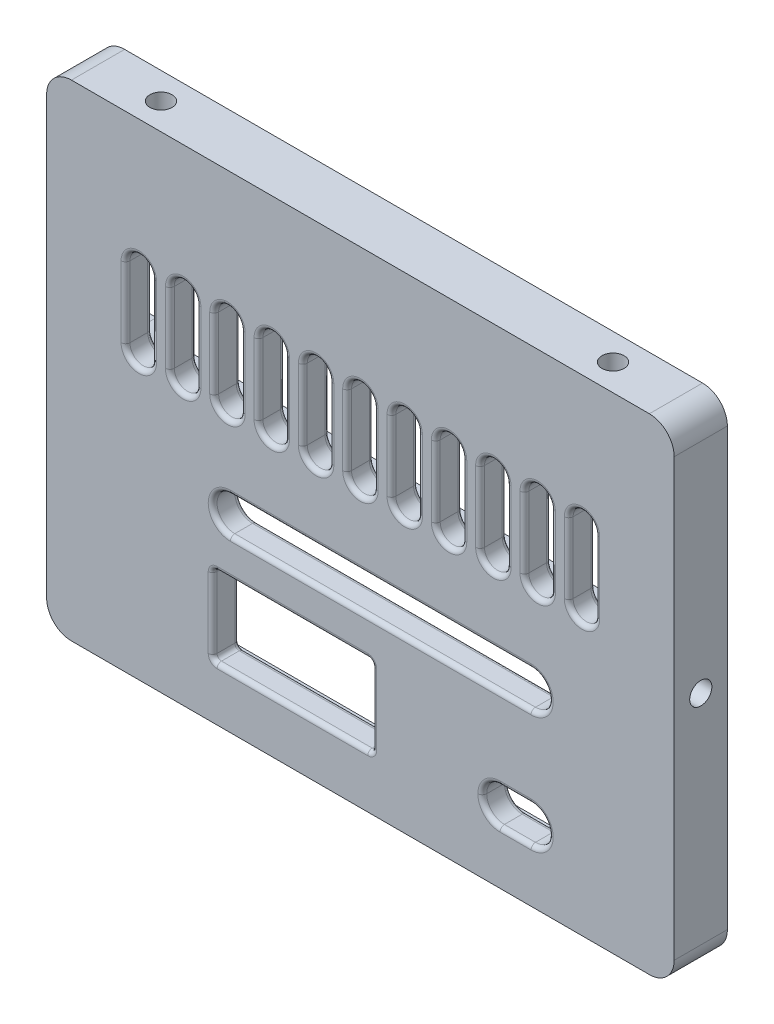
SolidWorks part; units mm, degrees
note: The reader was unsure of these and kept them because the rebuilt part matched: shared geometry of "Эскиз7<2>", "Эскиз9<2>".
ref_plane "Спереди" through (0, 0, 0) normal (0, 0, 1) x (1, 0, 0)
ref_plane "Сверху" through (0, 0, 0) normal (0, 1, 0) x (1, 0, 0)
ref_plane "Справа" through (0, 0, 0) normal (1, 0, 0) x (0, 0, -1)
sketch "Эскиз1" plane through (0, 0, 0) normal (0, 0, 1) x (1, 0, 0)
  line L0 (-32.6, 27.4) -> (32.6, 27.4)
  line L1 (35.4, -24.6) -> (35.4, 24.6)
  line L2 (-32.6, -27.4) -> (32.6, -27.4)
  line L3 (-35.4, 24.6) -> (-35.4, -24.6)
  arc A0 (-32.6, 27.4) -> (-35.4, 24.6) centre (-32.6, 24.6) ccw
  arc A1 (35.4, 24.6) -> (32.6, 27.4) centre (32.6, 24.6) ccw
  arc A2 (32.6, -27.4) -> (35.4, -24.6) centre (32.6, -24.6) ccw
  arc A3 (-35.4, -24.6) -> (-32.6, -27.4) centre (-32.6, -24.6) ccw
  point P11 (0, 27.4)
  point P14 (35.4, 0)
  point P17 (0, -27.4)
  point P20 (-35.4, 0)
  dimension "D3" = 2.8
  dimension "D1" = 70.8
  dimension "D2" = 54.8
extrude "Бобышка-Вытянуть1" add sketch "Эскиз1" along normal blind 3
sketch "Эскиз6" plane through (0, 0, 0) normal (0, 0, -1) x (-1, 0, 0)
  line L0 (-32.6, 27.4) -> (32.6, 27.4)
  line L1 (-35.4, 24.6) -> (-35.4, -24.6)
  line L2 (-32.6, -27.4) -> (32.6, -27.4)
  line L3 (35.4, -24.6) -> (35.4, 24.6)
  line L4 (-32.4, 24.4) -> (-28.5, 24.4)
  line L5 (32.4, -24.4) -> (32.4, -3)
  line L6 (-32.4, -24.4) -> (-28.5, -24.4)
  line L7 (-32.4, 24.4) -> (-32.4, 3)
  line L8 (0, 1.5) -> (0, -1.5) construction
  line L10 (-26.4, -1.5) -> (26.4, -1.5)
  line L11 (0, 32.9332) -> (0, -35.2988) construction
  line L12 (25.5, 21.9) -> (-25.5, 21.9) construction
  line L13 (25.5, -21.9) -> (-25.5, -21.9) construction
  line L14 (-22.5, 24.4) -> (22.5, 24.4)
  line L15 (-22.5, 16.4) -> (-28.5, 16.4)
  line L16 (-22.5, 16.4) -> (-22.5, 27.4)
  line L17 (-22.5, 27.4) -> (-28.5, 27.4)
  line L18 (-28.5, 16.4) -> (-28.5, 27.4)
  line L19 (-22.5, 16.4) -> (-28.5, 27.4) construction
  line L20 (-22.5, 27.4) -> (-28.5, 16.4) construction
  line L21 (22.5, 16.4) -> (28.5, 16.4)
  line L22 (22.5, 16.4) -> (22.5, 27.4)
  line L23 (22.5, 27.4) -> (28.5, 27.4)
  line L24 (28.5, 16.4) -> (28.5, 27.4)
  line L25 (22.5, 16.4) -> (28.5, 27.4) construction
  line L26 (22.5, 27.4) -> (28.5, 16.4) construction
  line L27 (22.5, -27.4) -> (28.5, -27.4)
  line L28 (22.5, -27.4) -> (22.5, -16.4)
  line L29 (22.5, -16.4) -> (28.5, -16.4)
  line L30 (28.5, -27.4) -> (28.5, -16.4)
  line L31 (22.5, -27.4) -> (28.5, -16.4) construction
  line L32 (22.5, -16.4) -> (28.5, -27.4) construction
  line L33 (-28.5, -27.4) -> (-22.5, -27.4)
  line L34 (-28.5, -27.4) -> (-28.5, -16.4)
  line L35 (-28.5, -16.4) -> (-22.5, -16.4)
  line L36 (-22.5, -27.4) -> (-22.5, -16.4)
  line L37 (-28.5, -27.4) -> (-22.5, -16.4) construction
  line L38 (-28.5, -16.4) -> (-22.5, -27.4) construction
  line L39 (-32.4, 24.4) -> (32.4, 24.4) construction
  line L40 (28.5, 24.4) -> (32.4, 24.4)
  line L41 (-32.4, -3) -> (-32.4, -24.4)
  line L42 (-32.4, 24.4) -> (-32.4, -24.4) construction
  line L43 (32.4, 3) -> (32.4, 24.4)
  line L44 (32.4, -24.4) -> (32.4, 24.4) construction
  line L45 (28.5, -24.4) -> (32.4, -24.4)
  line L46 (-32.4, -24.4) -> (32.4, -24.4) construction
  line L47 (-22.5, -24.4) -> (22.5, -24.4)
  line L48 (-2.6445, 0) -> (5.4228, 0) construction
  line L49 (-26.4, 1.5) -> (26.4, 1.5)
  line L50 (26.4, -3) -> (35.4, -3)
  line L51 (26.4, -3) -> (26.4, 3)
  line L52 (26.4, 3) -> (35.4, 3)
  line L53 (35.4, -3) -> (35.4, 3)
  line L54 (26.4, -3) -> (35.4, 3) construction
  line L55 (26.4, 3) -> (35.4, -3) construction
  line L56 (-26.4, -3) -> (-35.4, -3)
  line L57 (-26.4, -3) -> (-26.4, 3)
  line L58 (-26.4, 3) -> (-35.4, 3)
  line L59 (-35.4, -3) -> (-35.4, 3)
  line L60 (-26.4, -3) -> (-35.4, 3) construction
  line L61 (-26.4, 3) -> (-35.4, -3) construction
  arc A0 (-32.6, 27.4) -> (-35.4, 24.6) centre (-32.6, 24.6) ccw
  arc A1 (-35.4, -24.6) -> (-32.6, -27.4) centre (-32.6, -24.6) ccw
  arc A2 (32.6, -27.4) -> (35.4, -24.6) centre (32.6, -24.6) ccw
  arc A3 (35.4, 24.6) -> (32.6, 27.4) centre (32.6, 24.6) ccw
  arc A4 (32.4, 24.4) -> (32.4, 24.4) centre (32.4, 24.4) ccw
  arc A5 (32.4, -24.4) -> (32.4, -24.4) centre (32.4, -24.4) ccw
  arc A6 (-32.4, -24.4) -> (-32.4, -24.4) centre (-32.4, -24.4) ccw
  arc A7 (-32.4, 24.4) -> (-32.4, 24.4) centre (-32.4, 24.4) ccw
  point P38 (0, 0)
  point P48 (0, 21.9)
  point P51 (0, -21.9)
  point P75 (30.9, 0)
  point P81 (-30.9, 0)
  dimension "D3" = 6
  dimension "D4" = 11
  dimension "D5" = 51
  dimension "D6" = 6
  dimension "D7" = 9
  dimension "D2" = 3
extrude "Бобышка-Вытянуть3" add sketch "Эскиз6" along normal blind 3
fillet "Скругление7" radius 3 12 edges at (28.5, -16.4, -1.5) (22.5, -16.4, -1.5) (-22.5, -16.4, -1.5) (-28.5, -16.4, -1.5) (-28.5, 16.4, -1.5) (-22.5, 16.4, -1.5) (28.5, 16.4, -1.5) (22.5, 16.4, -1.5) (-26.4, 3, -1.5) (-26.4, -3, -1.5) (26.4, 3, -1.5) (26.4, -3, -1.5)
fillet "Скругление8" radius 3 16 edges at (-28.5, -21.9, -3) (-27.6213, -17.2787, -3) (-22.5, -21.9, -3) (22.5, -21.9, -3) (23.3787, -17.2787, -3) (28.5, -21.9, -3) (28.5, 21.9, -3) (22.5, 21.9, -3) (23.3787, 17.2787, -3) (-22.5, 21.9, -3) (-28.5, 21.9, -3) (-27.6213, 17.2787, -3) (-23.3787, -17.2787, -3) (27.6213, -17.2787, -3) (27.6213, 17.2787, -3) (-23.3787, 17.2787, -3)
fillet "Скругление9" radius 3 16 edges at (28.5, -21.9, 0) (22.5, -21.9, 0) (23.3787, -17.2787, 0) (-22.5, -21.9, 0) (-28.5, -21.9, 0) (-27.6213, -17.2787, 0) (-28.5, 21.9, 0) (-27.6213, 17.2787, 0) (-22.5, 21.9, 0) (22.5, 21.9, 0) (23.3787, 17.2787, 0) (28.5, 21.9, 0) (27.6213, -17.2787, 0) (-23.3787, -17.2787, 0) (-23.3787, 17.2787, 0) (27.6213, 17.2787, 0)
sketch "Эскиз7" plane through (0, -27.4, 0) normal (0, -1, 0) x (1, 0, 0)
  line L0 (0, 26.5617) -> (0, -19.5255) construction
  line L1 (25.5, 0) -> (-25.5, 0) construction
  circle A0 centre (-25.5, 0) radius 1.25
  circle A1 centre (25.5, 0) radius 1.25
  point P6 (0, 0)
  dimension "D2" = 2.5
  dimension "D1" = 51
extrude "Вырез-Вытянуть6" cut sketch "Эскиз7" against normal blind 9
extrude "Вырез-Вытянуть7" cut sketch "Эскиз7<2>" along normal blind 9 from offset 54.8 offset against normal yes
sketch "Эскиз7<2>" plane through (0, -27.4, 0) normal (0, -1, 0) x (1, 0, 0) same geometry as "Эскиз7"
sketch "Эскиз9" plane through (35.4, 0, 0) normal (1, 0, 0) x (0, 0, -1)
  circle A0 centre (0, 0) radius 1.25
  dimension "D1" = 2.5
extrude "Вырез-Вытянуть9" cut sketch "Эскиз9" against normal blind 7
extrude "Вырез-Вытянуть10" cut sketch "Эскиз9<2>" along normal blind 7 from offset 70.8 offset against normal yes
sketch "Эскиз9<2>" plane through (35.4, 0, 0) normal (1, 0, 0) x (0, 0, -1) same geometry as "Эскиз9"
sketch "Эскиз10" plane through (0, 0, 3) normal (0, 0, 1) x (1, 0, 0)
  line L0 (-47.1202, 8.54) -> (60.2518, 8.54) construction
  line L1 (-32.6, -27.4) -> (32.6, -27.4) construction
  line L2 (0, 11.8501) -> (0, -8.9997) construction
  line L3 (0, 12.54) -> (0, 4.54) construction
  line L4 (1.5, 12.54) -> (1.5, 4.54)
  line L5 (-1.5, 12.54) -> (-1.5, 4.54)
  line L6 (5, 12.54) -> (5, 4.54) construction
  line L7 (6.5, 12.54) -> (6.5, 4.54)
  line L8 (3.5, 12.54) -> (3.5, 4.54)
  line L9 (10, 12.54) -> (10, 4.54) construction
  line L10 (11.5, 12.54) -> (11.5, 4.54)
  line L11 (8.5, 12.54) -> (8.5, 4.54)
  line L12 (15, 12.54) -> (15, 4.54) construction
  line L13 (16.5, 12.54) -> (16.5, 4.54)
  line L14 (13.5, 12.54) -> (13.5, 4.54)
  line L15 (20, 12.54) -> (20, 4.54) construction
  line L16 (21.5, 12.54) -> (21.5, 4.54)
  line L17 (18.5, 12.54) -> (18.5, 4.54)
  line L18 (25, 12.54) -> (25, 4.54) construction
  line L19 (26.5, 12.54) -> (26.5, 4.54)
  line L20 (23.5, 12.54) -> (23.5, 4.54)
  line L21 (-5, 12.54) -> (-5, 4.54) construction
  line L22 (-3.5, 12.54) -> (-3.5, 4.54)
  line L23 (-6.5, 12.54) -> (-6.5, 4.54)
  line L24 (-10, 12.54) -> (-10, 4.54) construction
  line L25 (-8.5, 12.54) -> (-8.5, 4.54)
  line L26 (-11.5, 12.54) -> (-11.5, 4.54)
  line L27 (-15, 12.54) -> (-15, 4.54) construction
  line L28 (-13.5, 12.54) -> (-13.5, 4.54)
  line L29 (-16.5, 12.54) -> (-16.5, 4.54)
  line L30 (-20, 12.54) -> (-20, 4.54) construction
  line L31 (-18.5, 12.54) -> (-18.5, 4.54)
  line L32 (-21.5, 12.54) -> (-21.5, 4.54)
  line L33 (-25, 12.54) -> (-25, 4.54) construction
  line L34 (-23.5, 12.54) -> (-23.5, 4.54)
  line L35 (-26.5, 12.54) -> (-26.5, 4.54)
  arc A0 (1.5, 12.54) -> (-1.5, 12.54) centre (0, 12.54) ccw
  arc A1 (-1.5, 4.54) -> (1.5, 4.54) centre (0, 4.54) ccw
  arc A2 (6.5, 12.54) -> (3.5, 12.54) centre (5, 12.54) ccw
  arc A3 (3.5, 4.54) -> (6.5, 4.54) centre (5, 4.54) ccw
  arc A4 (11.5, 12.54) -> (8.5, 12.54) centre (10, 12.54) ccw
  arc A5 (8.5, 4.54) -> (11.5, 4.54) centre (10, 4.54) ccw
  arc A6 (16.5, 12.54) -> (13.5, 12.54) centre (15, 12.54) ccw
  arc A7 (13.5, 4.54) -> (16.5, 4.54) centre (15, 4.54) ccw
  arc A8 (21.5, 12.54) -> (18.5, 12.54) centre (20, 12.54) ccw
  arc A9 (18.5, 4.54) -> (21.5, 4.54) centre (20, 4.54) ccw
  arc A10 (26.5, 12.54) -> (23.5, 12.54) centre (25, 12.54) ccw
  arc A11 (23.5, 4.54) -> (26.5, 4.54) centre (25, 4.54) ccw
  arc A12 (-3.5, 12.54) -> (-6.5, 12.54) centre (-5, 12.54) ccw
  arc A13 (-6.5, 4.54) -> (-3.5, 4.54) centre (-5, 4.54) ccw
  arc A14 (-8.5, 12.54) -> (-11.5, 12.54) centre (-10, 12.54) ccw
  arc A15 (-11.5, 4.54) -> (-8.5, 4.54) centre (-10, 4.54) ccw
  arc A16 (-13.5, 12.54) -> (-16.5, 12.54) centre (-15, 12.54) ccw
  arc A17 (-16.5, 4.54) -> (-13.5, 4.54) centre (-15, 4.54) ccw
  arc A18 (-18.5, 12.54) -> (-21.5, 12.54) centre (-20, 12.54) ccw
  arc A19 (-21.5, 4.54) -> (-18.5, 4.54) centre (-20, 4.54) ccw
  arc A20 (-23.5, 12.54) -> (-26.5, 12.54) centre (-25, 12.54) ccw
  arc A21 (-26.5, 4.54) -> (-23.5, 4.54) centre (-25, 4.54) ccw
  point P9 (0, 8.54)
  point P17 (5, 8.54)
  point P24 (10, 8.54)
  point P31 (15, 8.54)
  point P38 (20, 8.54)
  point P45 (25, 8.54)
  point P52 (-5, 8.54)
  point P59 (-10, 8.54)
  point P66 (-15, 8.54)
  point P73 (-20, 8.54)
  point P80 (-25, 8.54)
  dimension "D1" = 35.94
  dimension "D2" = 8
  dimension "D3" = 3
  dimension "D4" = 6
  dimension "D5" = 6
extrude "Вырез-Вытянуть11" cut sketch "Эскиз10" against normal through all
sketch "Эскиз11" plane through (0, 0, 0) normal (0, 0, -1) x (-1, 0, 0)
  line L0 (0, 34.1399) -> (0, -47.428) construction
  line L1 (22.67, 34.6303) -> (22.67, -36.7984) construction
  line L2 (7.67, 34.6303) -> (7.67, -36.7984) construction
  line L3 (-20.3038, -24.4) -> (20.3038, -24.4) construction
  line L4 (-1.33, -21.4) -> (16.67, -21.4)
  line L5 (-1.33, -21.4) -> (-1.33, -12.4)
  line L6 (-1.33, -12.4) -> (16.67, -12.4)
  line L7 (16.67, -21.4) -> (16.67, -12.4)
  line L8 (-1.33, -21.4) -> (16.67, -12.4) construction
  line L9 (-1.33, -12.4) -> (16.67, -21.4) construction
  line L10 (-17.5, -8.8778) -> (-17.5, -39.9321) construction
  line L11 (-2.5003, -19.4) -> (37.4574, -19.4) construction
  line L14 (-13.75, -17.4) -> (-21.25, -17.4)
  line L15 (-13.75, -17.4) -> (-13.75, -21.4)
  line L16 (-13.75, -21.4) -> (-21.25, -21.4)
  line L17 (-21.25, -17.4) -> (-21.25, -21.4)
  line L18 (-13.75, -17.4) -> (-21.25, -21.4) construction
  line L19 (-13.75, -21.4) -> (-21.25, -17.4) construction
  point P7 (7.67, -16.9)
  point P20 (-17.5, -19.4)
  dimension "D3" = 18
  dimension "D4" = 9
  dimension "D5" = 3
  dimension "D8" = 7.5
  dimension "D9" = 4
  dimension "D7" = 3
  dimension "D1" = 22.67
  dimension "D2" = 15
  dimension "D6" = 17.5
extrude "Вырез-Вытянуть12" cut sketch "Эскиз11" against normal through all from offset 10
sketch "Эскиз13" plane through (0, 0, 0) normal (0, 0, -1) x (-1, 0, 0)
  line L0 (-19.25, -6.2) -> (14.67, -6.2) construction
  line L1 (-19.25, -4.2) -> (14.67, -4.2)
  line L2 (-19.25, -8.2) -> (14.67, -8.2)
  line L5 (-48.4357, 0) -> (52.8192, 0) construction
  line L6 (-9.8023, -12.4) -> (-9.8023, 0) construction
  line L7 (16.67, -12.4) -> (-1.33, -12.4) construction
  line L8 (-21.25, -17.4) -> (-21.25, -21.4) construction
  line L12 (16.67, -12.4) -> (16.67, -21.4) construction
  arc A0 (-19.25, -4.2) -> (-19.25, -8.2) centre (-19.25, -6.2) ccw
  arc A1 (14.67, -8.2) -> (14.67, -4.2) centre (14.67, -6.2) ccw
  point P2 (-2.29, -6.2)
  point P18 (-9.8023, -6.2)
  dimension "D1" = 4
extrude "Вырез-Вытянуть13" cut sketch "Эскиз13" against normal through all
fillet "Скругление12" radius 0.5 88 edges at (-25, 14.04, 3) (-23.5, 8.54, 3) (-25, 3.04, 3) (-25, 3.04, 0) (-26.5, 8.54, 0) (-25, 14.04, 0) (-20, 14.04, 3) (-18.5, 8.54, 3) (-20, 3.04, 3) (-20, 3.04, 0) (-21.5, 8.54, 0) (-20, 14.04, 0) (-15, 14.04, 3) (-13.5, 8.54, 3) (-15, 3.04, 3) (-15, 3.04, 0) (-16.5, 8.54, 0) (-15, 14.04, 0) (-10, 14.04, 3) (-8.5, 8.54, 3) (-10, 3.04, 3) (-10, 3.04, 0) (-11.5, 8.54, 0) (-10, 14.04, 0) (-5, 14.04, 3) (-3.5, 8.54, 3) (-5, 3.04, 3) (-5, 3.04, 0) (-6.5, 8.54, 0) (-5, 14.04, 0) (0, 14.04, 3) (1.5, 8.54, 3) (0, 3.04, 3) (0, 3.04, 0) (-1.5, 8.54, 0) (0, 14.04, 0) (5, 14.04, 3) (6.5, 8.54, 3) (5, 3.04, 3) (5, 3.04, 0) (3.5, 8.54, 0) (5, 14.04, 0) (10, 14.04, 3) (11.5, 8.54, 3) (10, 3.04, 3) (10, 3.04, 0) (8.5, 8.54, 0) (10, 14.04, 0) (15, 14.04, 3) (16.5, 8.54, 3) (15, 3.04, 3) (20, 14.04, 3) (21.5, 8.54, 3) (20, 3.04, 3) (25, 14.04, 3) (26.5, 8.54, 3) (25, 3.04, 3) (25, 14.04, 0) (26.5, 8.54, 0) (25, 3.04, 0) (20, 14.04, 0) (21.5, 8.54, 0) (20, 3.04, 0) (15, 14.04, 0) (16.5, 8.54, 0) (15, 3.04, 0) (-26.5, 8.54, 3) (-23.5, 8.54, 0) (-21.5, 8.54, 3) (-18.5, 8.54, 0) (-16.5, 8.54, 3) (-13.5, 8.54, 0) (-11.5, 8.54, 3) (-8.5, 8.54, 0) (-6.5, 8.54, 3) (-3.5, 8.54, 0) (-1.5, 8.54, 3) (1.5, 8.54, 0) (3.5, 8.54, 3) (6.5, 8.54, 0) (8.5, 8.54, 3) (11.5, 8.54, 0) (13.5, 8.54, 3) (18.5, 8.54, 3) (23.5, 8.54, 3) (23.5, 8.54, 0) (18.5, 8.54, 0) (13.5, 8.54, 0)
fillet "Скругление10" radius 2 4 edges at (21.25, -21.4, 1.4234) (13.75, -21.4, 1.5) (13.75, -17.4, 1.5) (21.25, -17.4, 1.4791)
fillet "Скругление11" radius 0.5 34 edges at (-7.67, -12.4, 3) (-7.67, -12.4, 0) (1.33, -16.9, 3) (-16.67, -16.9, 3) (1.33, -16.9, 0) (-16.67, -16.9, 0) (19.7979, -21.3235, 0) (19.9337, -17.5205, 0) (17.5, -17.4, 0) (14.3358, -17.9858, 0) (14.3358, -20.8142, 0) (20.6642, -20.8142, 3) (20.6642, -17.9858, 3) (17.5, -17.4, 3) (14.3358, -17.9858, 3) (14.3358, -20.8142, 3) (-7.67, -21.4, 3) (-7.67, -21.4, 0) (-16.67, -12.4, 1.5) (1.33, -12.4, 1.5) (1.33, -21.4, 1.5) (-16.67, -21.4, 1.5) (17.5, -21.4, 0) (17.5, -21.4, 3) (21.25, -6.2, 0) (2.29, -4.2, 0) (-16.67, -6.2, 0) (21.25, -6.2, 3) (2.29, -4.2, 3) (-16.67, -6.2, 3) (2.29, -8.2, 0) (2.29, -8.2, 3) (21.1438, -18.7568, -0.1066) (20.7974, -20.6671, -0.0409)
equation "\"Ширина короба\" = 71"
equation "\"Высота короба\"= 55"
equation "\"Зазор\"= 0.2"
equation "\"D1@Эскиз1\" = \"Ширина короба\" - \"Зазор\""
equation "\"D2@Эскиз1\"=\"Высота короба\"-\"Зазор\""
equation "\"D3@Эскиз1\"=5-2-\"Зазор\""
equation "\"D5@Эскиз6\"=\"Ширина короба\"-10*2"
equation "\"D1@Эскиз7\"= \"Ширина короба\" - 10 * 2"
equation "\"D19@Вырез-Вытянуть7\"=\"Высота короба\"-\"Зазор\""
equation "\"D19@Вырез-Вытянуть10\"=\"Ширина короба\"-\"Зазор\""
equation "\"D1@Эскиз10\"=-0.2+3+2+8.5+2.54+2+10.1+2+(12/2)"
equation "\"D1@Эскиз11\"=53.34/2-4"
equation "\"D7@Эскиз11\"=3"
